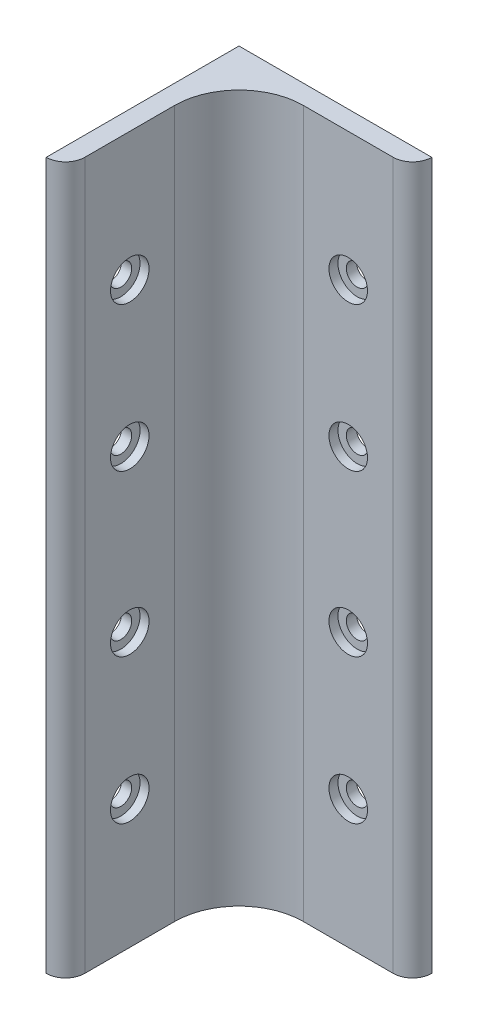
SolidWorks part; units mm, degrees
material "PLA"
ref_plane "Front Plane" through (0, 0, 0) normal (0, 0, 1) x (1, 0, 0)
ref_plane "Top Plane" through (0, 0, 0) normal (0, 1, 0) x (1, 0, 0)
ref_plane "Right Plane" through (0, 0, 0) normal (1, 0, 0) x (0, 0, -1)
sketch "Sketch1" plane through (0, 0, 0) normal (0, 1, 0) x (1, 0, 0)
  line L0 (0, 0) -> (0, -30)
  line L1 (0, 0) -> (30, 0)
  line L2 (0, -30) -> (3, -30)
  line L3 (3, -30) -> (3, -3)
  line L4 (3, -3) -> (30, -3)
  line L5 (30, -3) -> (30, 0)
  dimension "D1" = 30
  dimension "D2" = 3
extrude "Boss-Extrude1" add sketch "Sketch1" along normal blind 110
fillet "Fillet1" radius 10 1 edges at (3, 55, 3)
fillet "Fillet2" radius 3 2 edges at (3, 55, 30) (30, 55, 3)
sketch "Sketch2" plane through (0, 0, 3) normal (0, 0, 1) x (1, 0, 0)
  line L0 (0, 110) -> (0, 0) construction
  line L1 (13, 110) -> (27, 110) construction
  line L2 (0, 55) -> (50000, 55) construction
  line L3 (18.9655, 78.75) -> (50018.9655, 78.75) construction
  circle A0 centre (20, 90) radius 1.7
  circle A1 centre (20, 67.5) radius 1.7
  circle A2 centre (20, 42.5) radius 1.7
  circle A3 centre (20, 20) radius 1.7
  point P8 (0, 55)
  dimension "D2" = 3.4
  dimension "D1" = 20
  dimension "D3" = 20
  dimension "D4" = 11.25
extrude "Cut-Extrude1" cut sketch "Sketch2" against normal through all
sketch "Sketch3" plane through (3, 0, 0) normal (1, 0, 0) x (0, 0, -1)
  line L0 (-30, 55) -> (49970, 55) construction
  line L1 (-30, 110) -> (-30, 0) construction
  line L2 (-22.1346, 78.75) -> (49977.8654, 78.75) construction
  line L3 (-27, 110) -> (-13, 110) construction
  line L4 (0, 110) -> (0, 0) construction
  circle A0 centre (-20, 90) radius 1.7
  circle A1 centre (-20, 67.5) radius 1.7
  circle A2 centre (-20, 42.5) radius 1.7
  circle A3 centre (-20, 20) radius 1.7
  point P4 (-30, 55)
  dimension "D3" = 3.4
  dimension "D1" = 11.25
  dimension "D2" = 20
  dimension "D4" = 20
extrude "Cut-Extrude2" cut sketch "Sketch3" against normal through all
sketch "Sketch4" plane through (0, 0, 3) normal (0, 0, 1) x (1, 0, 0)
  line L0 (27, 55) -> (50027, 55) construction
  line L1 (27, 0) -> (27, 110) construction
  line L3 (20, 78.75) -> (50020, 78.75) construction
  circle A0 centre (20, 90) radius 3
  circle A1 centre (20, 67.5) radius 3
  circle A2 centre (20, 42.5) radius 3
  circle A3 centre (20, 20) radius 3
  point P7 (27, 55)
  dimension "D1" = 6
  dimension "D2" = 23.75
extrude "Cut-Extrude3" cut sketch "Sketch4" against normal blind 1.4
sketch "Sketch5" plane through (3, 0, 0) normal (1, 0, 0) x (0, 0, -1)
  line L0 (-27, 55) -> (49973, 55) construction
  line L1 (-27, 110) -> (-27, 0) construction
  line L2 (-37.3606, 78.75) -> (49962.6394, 78.75) construction
  circle A0 centre (-20, 90) radius 3
  circle A1 centre (-20, 67.5) radius 3
  circle A2 centre (-20, 42.5) radius 3
  circle A3 centre (-20, 20) radius 3
  point P7 (-27, 55)
  dimension "D1" = 6
  dimension "D2" = 23.75
extrude "Cut-Extrude4" cut sketch "Sketch5" against normal blind 1.4
